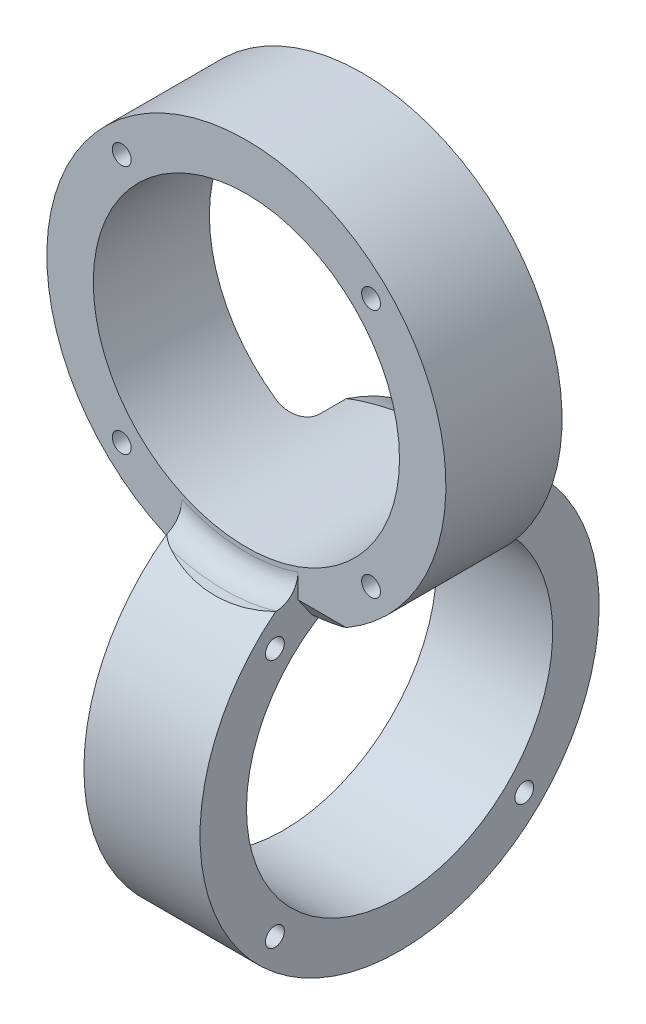
SolidWorks part; units mm, degrees
ref_plane "Front Plane" through (0, 0, 0) normal (0, 0, 1) x (1, 0, 0)
ref_plane "Top Plane" through (0, 0, 0) normal (0, 1, 0) x (1, 0, 0)
ref_plane "Right Plane" through (0, 0, 0) normal (1, 0, 0) x (0, 0, -1)
sketch "Sketch1" plane through (0, 0, 0) normal (0, 0, 1) x (1, 0, 0)
  arc A0 (21.1, 0) -> (-21.1, 0) centre (0, 0) ccw
  arc A4 (-21.1, 0) -> (21.1, 0) centre (0, 0) ccw
  circle A6 centre (0, 0) radius 27.5
  dimension "D1" = 55
  dimension "D2" = 21.1
extrude "Firstring" add sketch "Sketch1" along normal blind 16
ref_plane "SecondringBasePlane" through (7.11, 0, 0) normal (1, 0, 0) x (0, 0, -1)
sketch "Sketch6" plane through (7.11, 0, 0) normal (1, 0, 0) x (0, 0, -1)
  line L0 (0, 0) -> (0, -45.2308) construction
  line L1 (0, -45.2308) -> (-2, -45.2308) construction
  circle A0 centre (-2, -45.2308) radius 21.1
  circle A2 centre (-2, -45.2308) radius 27.5
  dimension "D3" = 42.2
  dimension "D4" = 55
  dimension "D1" = 45.2308
  dimension "D2" = 2
extrude "SecondRing" add sketch "Sketch6" against normal blind 16
sketch "Sketch7" plane through (0, 0, 0) normal (0, 0, -1) x (-1, 0, 0)
  circle A0 centre (0, 0) radius 21.1
  arc A1 (-21.1, 0) -> (21.1, 0) centre (0, 0) ccw construction
extrude "ClearIDFirstRing" cut sketch "Sketch7" against normal through all both and the other way through all
sketch "Sketch8" plane through (7.11, 0, 0) normal (1, 0, 0) x (0, 0, -1)
  circle A0 centre (-2, -45.2308) radius 21.1
  circle A1 centre (-2, -45.2308) radius 21.1 construction
extrude "ClearIDSecondRing" cut sketch "Sketch8" against normal through all both and the other way through all
sketch "Sketch9" plane through (0, 0, 16) normal (0, 0, 1) x (1, 0, 0)
  line L0 (-19.4454, 19.4454) -> (-14.92, 14.92) construction
  line L1 (0, 0) -> (-47.9615, 0) construction
  circle A0 centre (0, 0) radius 27.5 construction
  circle A1 centre (0, 0) radius 21.1 construction
  arc A2 (7.11, -26.565) -> (-8.89, -26.0234) centre (0, 0) ccw construction
  circle A3 centre (0, 0) radius 21.1 construction
  circle A4 centre (0, 0) radius 24.3 construction
  circle A5 centre (-17.1827, 17.1827) radius 1.3
  circle A6 centre (17.1827, 17.1827) radius 1.3
  circle A7 centre (17.1827, -17.1827) radius 1.3
  circle A8 centre (-17.1827, -17.1827) radius 1.3
  point P11 (-17.1827, 17.1827)
  point P27 (0, 0)
  dimension "D2" = 2.6
  dimension "D4" = 48.6
  dimension "D1" = 45
  dimension "D3" = 4
extrude "FirstRingHoles" cut sketch "Sketch9" against normal through all both and the other way through all
sketch "Sketch10" plane through (0, 0, 16) normal (0, 0, 1) x (1, 0, 0)
  circle A0 centre (0, 0) radius 24.7237
  arc A1 (7.11, -26.565) -> (-8.89, -26.0234) centre (0, 0) ccw construction
extrude "Cut-Extrude5" cut sketch "Sketch10" along normal through all
fillet "Fillet1" radius 3 1 edges at (-0.9407, -24.7058, 16)
fillet "Fillet2" radius 3 2 edges at (-8.89, -21.6808, 0) (7.11, -22.0459, 0)
fillet "Fillet3" [suppressed] radius 2
sketch "Sketch11" plane through (-8.89, 0, 0) normal (-1, 0, 0) x (0, 0, 1)
  line L0 (-59.7716, -45.2308) -> (-25.06, -45.2308) construction
  line L1 (2, -45.2308) -> (-15.1827, -28.0481) construction
  circle A0 centre (2, -45.2308) radius 24.3 construction
  arc A1 (-3, -24.7317) -> (10.7343, -26.0234) centre (2, -45.2308) ccw construction
  circle A2 centre (-15.1827, -28.0481) radius 1.3
  circle A3 centre (19.1827, -28.0481) radius 1.3
  circle A4 centre (19.1827, -62.4135) radius 1.3
  circle A5 centre (-15.1827, -62.4135) radius 1.3
  point P20 (2, -45.2308)
  dimension "D1" = 48.6
  dimension "D3" = 2.6
  dimension "D2" = 45
  dimension "D4" = 4
extrude "Cut-Extrude6" cut sketch "Sketch11" against normal through all
sketch "Sketch12" plane through (7.11, 0, 0) normal (1, 0, 0) x (0, 0, -1)
  line L0 (-13.4584, -27.446) -> (-17.0831, -22.2693)
  line L1 (-13.4584, -34.6684) -> (-13.4584, -21.4538) construction
  line L2 (-13.4584, -27.446) -> (-17.6257, -27.446)
  line L3 (-17.6257, -27.446) -> (-17.0831, -22.2693)
  dimension "D1" = 35
extrude "Cut-Extrude7" cut sketch "Sketch12" along normal through all
sketch3d "3DSketch1"
  line L0 (27.5, 31.8389, 16) -> (27.5, -50.5297, 16) construction
  line L1 (7.11, -53.5944, 29.5) -> (7.11, -26.1944, 29.5) construction
  arc A0 (13.7492, -23.8162, 16) -> (-8.89, -26.0234, 16) centre (0, 0, 16) ccw construction
  arc A1 (7.11, -23.6793, 19.0818) -> (7.11, -19.866, -8.6244) centre (7.11, -45.2308, 2) ccw construction
  point P0 (27.5, 0, 16)
  point P1 (7.11, -45.2308, 29.5)
  point P3 (0, 0, 0)
  point P7 (0, 0, 43.5)
  point P12 (34.61, -45.2308, 2)
  point P13 (27.5, -50.5297, 16)
ref_plane "Plane1" through (15.746, 0, 23.7822) normal (-0.5521, 0, -0.8338) x (-0.8338, 0, 0.5521)
